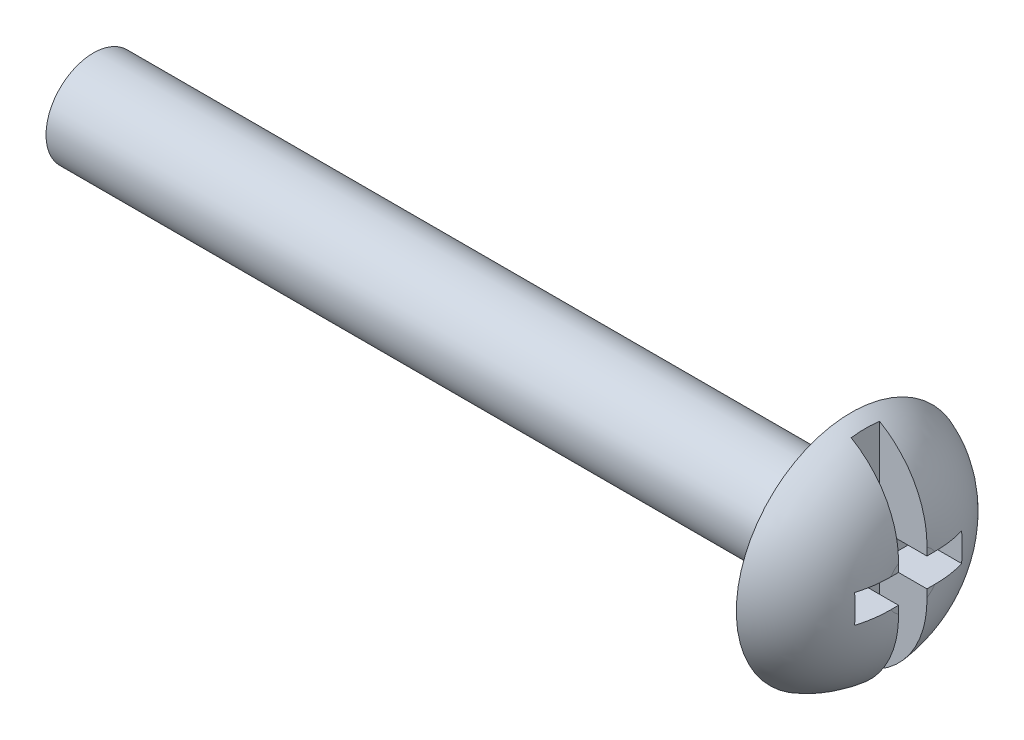
SolidWorks part; units mm, degrees
ref_plane "Front Plane" through (0, 0, 0) normal (0, 0, 1) x (1, 0, 0)
ref_plane "Top Plane" through (0, 0, 0) normal (0, 1, 0) x (1, 0, 0)
ref_plane "Right Plane" through (0, 0, 0) normal (1, 0, 0) x (0, 0, -1)
sketch "Sketch1" plane through (0, 0, 0) normal (1, 0, 0) x (0, 0, -1)
  circle A0 centre (0, 0) radius 4.85
extrude "Boss-Extrude1" add sketch "Sketch1" along normal blind 2.6
sketch "Sketch4" plane through (0, 0, 0) normal (-1, 0, 0) x (0, 0, 1)
  circle A0 centre (0, 0) radius 2
extrude "Boss-Extrude3" add sketch "Sketch4" along normal blind 32
fillet "Fillet1" radius 4 1 edges at (2.6, 0, -4.85)
sketch "Sketch5" plane through (2.6, 0, 0) normal (1, 0, 0) x (0, 0, -1)
  line L0 (-0.6, 0.6) -> (-2.2589, 0.6)
  line L1 (0.6, -5.0707) -> (-0.6, -5.0707)
  line L2 (0.6, -5.0707) -> (0.6, -0.6)
  line L3 (0.6, 5.0707) -> (-0.6, 5.0707)
  line L4 (-0.6, -5.0707) -> (-0.6, -0.6)
  line L5 (0.6, -5.0707) -> (-0.6, 5.0707) construction
  line L6 (0.6, 5.0707) -> (-0.6, -5.0707) construction
  line L7 (2.2589, 0.6) -> (0.6, 0.6)
  line L8 (2.2589, 0.6) -> (2.2589, -0.6)
  line L9 (2.2589, -0.6) -> (0.6, -0.6)
  line L10 (-2.2589, 0.6) -> (-2.2589, -0.6)
  line L11 (2.2589, 0.6) -> (-2.2589, -0.6) construction
  line L12 (2.2589, -0.6) -> (-2.2589, 0.6) construction
  line L13 (-0.6, -0.6) -> (-2.2589, -0.6)
  line L14 (-0.6, 0.6) -> (-0.6, 5.0707)
  line L15 (0.6, 0.6) -> (0.6, 5.0707)
  point P0 (0, 0)
  point P6 (0, 0)
extrude "Cut-Extrude1" cut sketch "Sketch5" against normal blind 2
